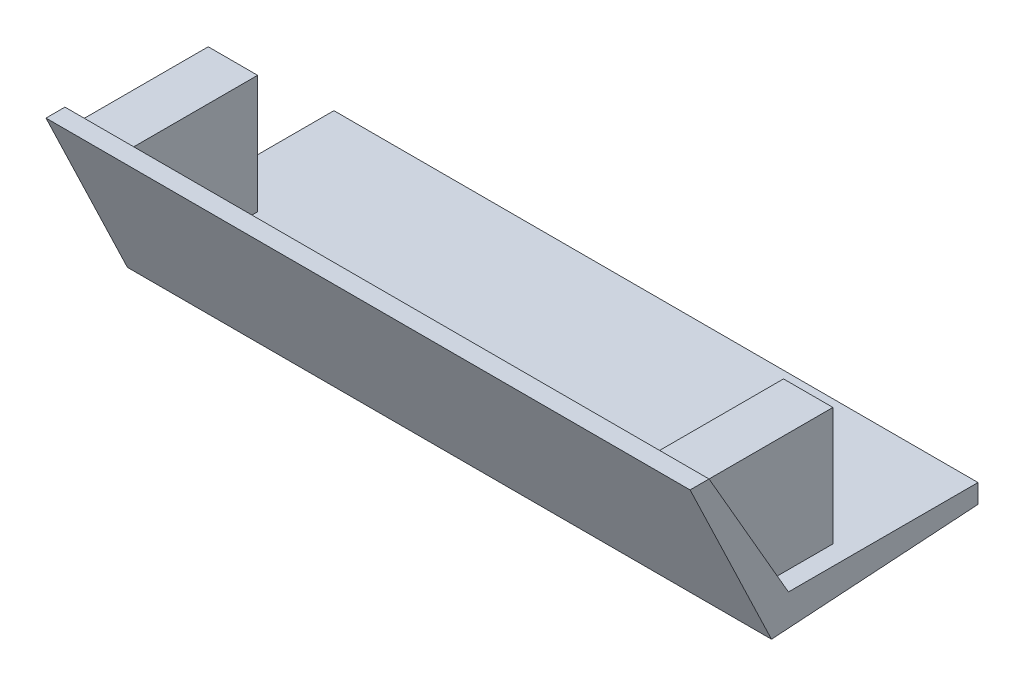
SolidWorks part; units mm, degrees
ref_plane "Front Plane" through (0, 0, 0) normal (0, 0, 1) x (1, 0, 0)
ref_plane "Top Plane" through (0, 0, 0) normal (0, 1, 0) x (1, 0, 0)
ref_plane "Right Plane" through (0, 0, 0) normal (1, 0, 0) x (0, 0, -1)
sketch "Sketch1" plane through (0, 0, 0) normal (1, 0, 0) x (0, 0, -1)
  line L0 (0, 0) -> (-29.3294, 50.8)
  line L1 (0, 0) -> (70, 0)
  line L2 (-29.3294, 50.8) -> (-36.3294, 50.8)
  line L3 (-36.3294, 50.8) -> (-6.2529, -12)
  line L4 (-6.2529, -12) -> (70, -7)
  line L5 (70, -7) -> (70, 0)
  line L6 (-6.2529, -12) -> (-6.2529, 0) construction
  line L7 (-12, 0) -> (0, 0) construction
  point P8 (0, 0)
  dimension "D1" = 70
  dimension "D2" = 60
  dimension "D3" = 50.8
  dimension "D4" = 7
  dimension "D5" = 7
  dimension "D6" = 12
extrude "Boss-Extrude2" add sketch "Sketch1" along normal mid plane 237.85
sketch "Sketch2" plane through (0, 0, 0) normal (0, 0, 1) x (1, 0, 0)
  line L0 (0, 0) -> (0, 50.8) construction
  line L5 (115.75, 47.625) -> (96.7, 47.625) construction
  line L6 (115.75, 47.625) -> (115.75, 3.175) construction
  line L11 (115.75, 3.175) -> (96.7, 3.175) construction
  line L12 (96.7, 47.625) -> (96.7, 3.175) construction
  line L14 (115.35, 47.225) -> (115.35, 3.575)
  line L15 (115.35, 3.575) -> (97.1, 3.575)
  line L28 (97.1, 47.225) -> (97.1, 3.575)
  line L29 (115.35, 47.225) -> (97.1, 47.225)
  line L30 (-96.7, 47.625) -> (-96.7, 3.175) construction
  line L31 (-115.75, 3.175) -> (-96.7, 3.175) construction
  line L32 (-115.75, 47.625) -> (-115.75, 3.175) construction
  line L33 (-115.75, 47.625) -> (-96.7, 47.625) construction
  line L34 (-115.35, 47.225) -> (-97.1, 47.225)
  line L35 (-97.1, 47.225) -> (-97.1, 3.575)
  line L36 (-115.35, 3.575) -> (-97.1, 3.575)
  line L37 (-115.35, 47.225) -> (-115.35, 3.575)
  line L39 (118.925, 0) -> (-118.925, 0) construction
  line L40 (118.925, 50.8) -> (-118.925, 50.8) construction
  line L41 (118.925, 0) -> (118.925, 50.8) construction
  point P7 (0, 50.8)
  point P8 (0, 0)
  point P9 (0, 0)
  point P29 (0, 0)
  dimension "D2" = 19.05
  dimension "D3" = 44.45
  dimension "D6" = 3.175
  dimension "D4" = 3.175
  dimension "D7" = 3.175
  dimension "D1" = 193.4
  dimension "D5" = 0.4
extrude "Boss-Extrude1" add sketch "Sketch2" along normal up to surface and the other way blind 20 up to face at (0, 25.4, 14.6647)
equation "\"D1@Sketch2\"=187.05mm+0.25in"
